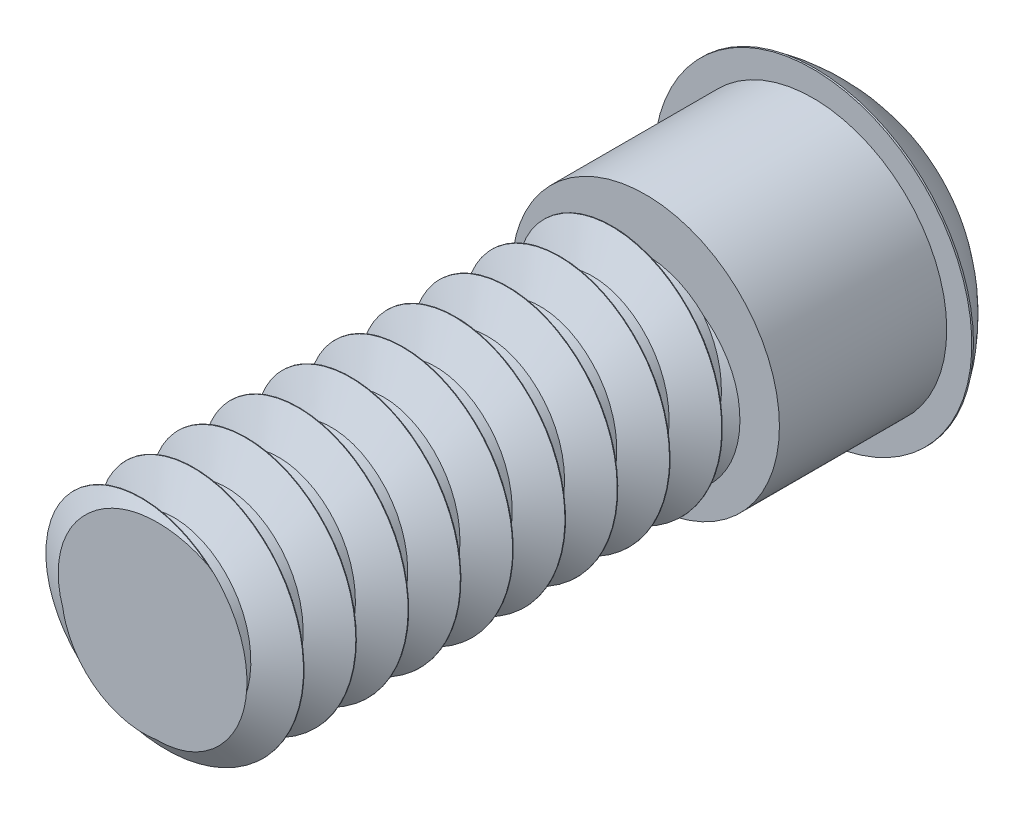
SolidWorks part; units mm, degrees
ref_plane "Front Plane" through (0, 0, 0) normal (0, 0, 1) x (1, 0, 0)
ref_plane "Top Plane" through (0, 0, 0) normal (0, 1, 0) x (1, 0, 0)
ref_plane "Right Plane" through (0, 0, 0) normal (1, 0, 0) x (0, 0, -1)
sketch "Sketch1" plane through (0, 0, 0) normal (0, 0, 1) x (1, 0, 0)
  circle A0 centre (0, 0) radius 1.7526
curve "Helix/Spiral1" pitch 0.7937 height 17.78 radius 1.7526 left hand yes centre (0, 0, 0) axis (0, 0, 1) start towards (0, 1, 0)
sketch "Sketch2" plane through (0, 0, 0) normal (0, 0, 1) x (1, 0, 0)
  circle A0 centre (0, 0) radius 1.7526
extrude "Boss-Extrude1" add sketch "Sketch2" along normal blind 7.62
sketch "Sketch3" plane through (0, 0, 0) normal (1, 0, 0) x (0, 0, -1)
  line L0 (-0.3925, 1.7526) -> (-0.0992, 1.2446)
  line L1 (-0.0992, 1.2446) -> (0.0992, 1.2446)
  line L2 (0.0992, 1.2446) -> (0.3925, 1.7526)
  line L3 (0.3925, 1.7526) -> (-0.3925, 1.7526)
  line L4 (0, 1.7526) -> (0, 1.2446) construction
  dimension "D1" = 60
  dimension "D2" = 0.508
  dimension "D3" = 0.1984
sweep "Cut-Sweep1" cut profiles "Sketch3" path "Helix/Spiral1" align with end faces yes
sketch "Sketch4" plane through (0, 0, 0) normal (0, 0, 1) x (1, 0, 0)
  circle A0 centre (0, 0) radius 2.032
extrude "Boss-Extrude2" add sketch "Sketch4" against normal blind 2.54
sketch "Sketch5" plane through (0, 0, -2.54) normal (0, 0, -1) x (-1, 0, 0)
  circle A0 centre (0, 0) radius 2.413
extrude "Boss-Extrude3" add sketch "Sketch5" along normal blind 0.0254
dome "Dome1" faces to dome 1 distance 1.27 reverse direction no elliptical dome no face at (-2.413, 0, -2.5654) parameters "D1"=1.27
